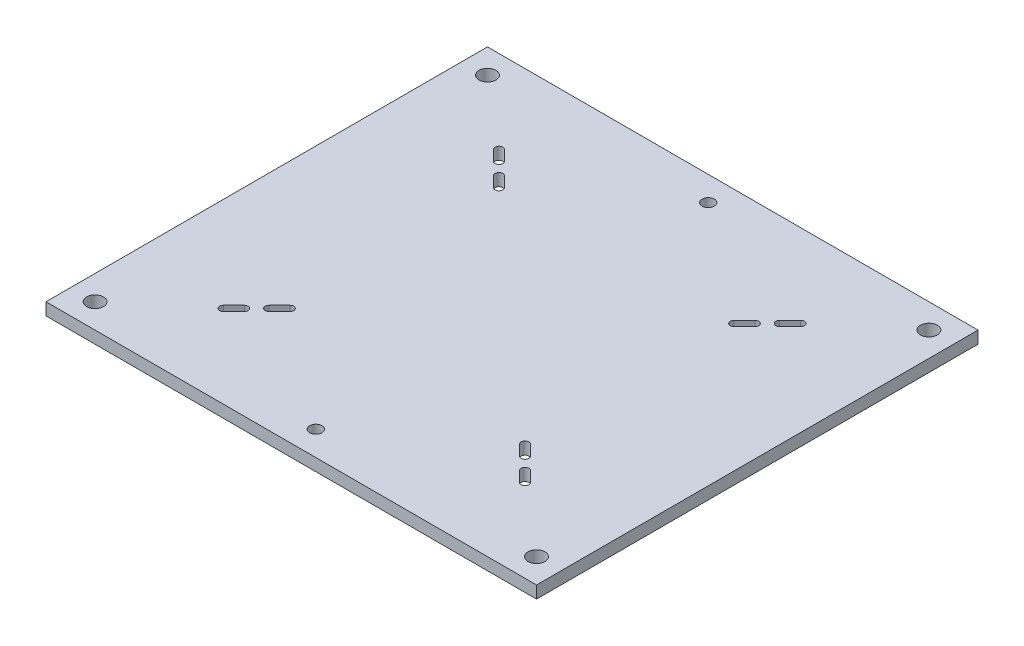
SolidWorks part; units mm, degrees
material "6061-T6 (SS)"
ref_plane "Front Plane" through (0, 0, 0) normal (0, 0, 1) x (1, 0, 0)
ref_plane "Top Plane" through (0, 0, 0) normal (0, 1, 0) x (1, 0, 0)
ref_plane "Right Plane" through (0, 0, 0) normal (1, 0, 0) x (0, 0, -1)
sketch "Sketch1" plane through (0, 0, 0) normal (0, 1, 0) x (1, 0, 0)
  line L1 (0, 0) -> (254, 0)
  line L2 (0, 0) -> (0, -228.6)
  line L3 (0, -228.6) -> (254, -228.6)
  line L4 (254, 0) -> (254, -228.6)
  dimension "D1" = 254
  dimension "D2" = 228.6
extrude "base plate" add sketch "Sketch1" against normal blind 6.35
sketch "center lines" plane through (0, 0, 0) normal (0, 1, 0) x (1, 0, 0)
  line L0 (127, 0) -> (127, -228.6) construction
  line L1 (254, 0) -> (0, 0) construction
  line L2 (0, -228.6) -> (254, -228.6) construction
  line L3 (0, -114.3) -> (254, -114.3) construction
  line L4 (0, 0) -> (0, -228.6) construction
  line L5 (254, -228.6) -> (254, 0) construction
sketch "Sketch3" plane through (0, 0, 0) normal (0, 1, 0) x (1, 0, 0)
  line L0 (36.125, -187.6487) -> (46.9013, -198.425)
  line L1 (46.9013, -198.425) -> (81.0263, -164.3)
  line L2 (81.0263, -164.3) -> (70.25, -153.5237)
  line L3 (70.25, -153.5237) -> (36.125, -187.6487)
  line L4 (48.9222, -185.6278) -> (54.3104, -180.2396) construction
  line L5 (47.508, -184.2135) -> (52.8962, -178.8254)
  line L6 (50.3365, -187.042) -> (55.7246, -181.6538)
  line L7 (0, -228.6) -> (254, -228.6) construction
  line L8 (66.1191, -168.4309) -> (60.7309, -173.8191) construction
  line L9 (67.5333, -169.8451) -> (62.1451, -175.2333)
  line L10 (127, 0) -> (127, -228.6) construction
  line L11 (0, -114.3) -> (254, -114.3) construction
  line L12 (81.0263, -64.3) -> (70.25, -75.0763)
  line L13 (46.9013, -30.175) -> (81.0263, -64.3)
  line L14 (36.125, -40.9513) -> (46.9013, -30.175)
  line L15 (70.25, -75.0763) -> (36.125, -40.9513)
  line L16 (207.0987, -30.175) -> (172.9737, -64.3)
  line L17 (217.875, -40.9513) -> (207.0987, -30.175)
  line L18 (183.75, -75.0763) -> (217.875, -40.9513)
  line L19 (172.9737, -64.3) -> (183.75, -75.0763)
  line L20 (172.9737, -164.3) -> (183.75, -153.5237)
  line L21 (207.0987, -198.425) -> (172.9737, -164.3)
  line L22 (217.875, -187.6487) -> (207.0987, -198.425)
  line L23 (183.75, -153.5237) -> (217.875, -187.6487)
  line L24 (64.7049, -167.0167) -> (59.3167, -172.4049)
  line L25 (48.9222, -42.9722) -> (54.3104, -48.3604) construction
  line L26 (47.508, -44.3865) -> (52.8962, -49.7746)
  line L27 (50.3365, -41.558) -> (55.7246, -46.9462)
  line L28 (66.1191, -60.1691) -> (60.7309, -54.7809) construction
  line L29 (67.5333, -58.7549) -> (62.1451, -53.3667)
  line L30 (64.7049, -61.5833) -> (59.3167, -56.1951)
  line L31 (205.0778, -42.9722) -> (199.6896, -48.3604) construction
  line L32 (206.492, -44.3865) -> (201.1038, -49.7746)
  line L33 (203.6635, -41.558) -> (198.2754, -46.9462)
  line L34 (187.8809, -60.1691) -> (193.2691, -54.7809) construction
  line L35 (186.4667, -58.7549) -> (191.8549, -53.3667)
  line L36 (189.2951, -61.5833) -> (194.6833, -56.1951)
  line L37 (187.8809, -168.4309) -> (193.2691, -173.8191) construction
  line L38 (186.4667, -169.8451) -> (191.8549, -175.2333)
  line L39 (189.2951, -167.0167) -> (194.6833, -172.4049)
  line L40 (205.0778, -185.6278) -> (199.6896, -180.2396) construction
  line L41 (206.492, -184.2135) -> (201.1038, -178.8254)
  line L42 (203.6635, -187.042) -> (198.2754, -181.6538)
  line L43 (70.25, -164.3) -> (70.25, -153.5237)
  line L44 (81.0263, -164.3) -> (70.25, -164.3)
  line L45 (70.25, -64.3) -> (70.25, -75.0763)
  line L46 (81.0263, -64.3) -> (70.25, -64.3)
  line L47 (183.75, -64.3) -> (183.75, -75.0763)
  line L48 (172.9737, -64.3) -> (183.75, -64.3)
  line L49 (183.75, -164.3) -> (183.75, -153.5237)
  line L50 (172.9737, -164.3) -> (183.75, -164.3)
  arc A0 (47.508, -184.2135) -> (50.3365, -187.042) centre (48.9222, -185.6278) ccw
  arc A1 (55.7246, -181.6538) -> (52.8962, -178.8254) centre (54.3104, -180.2396) ccw
  arc A2 (67.5333, -169.8451) -> (64.7049, -167.0167) centre (66.1191, -168.4309) ccw
  arc A3 (59.3167, -172.4049) -> (62.1451, -175.2333) centre (60.7309, -173.8191) ccw
  arc A4 (47.508, -44.3865) -> (50.3365, -41.558) centre (48.9222, -42.9722) cw
  arc A5 (55.7246, -46.9462) -> (52.8962, -49.7746) centre (54.3104, -48.3604) cw
  arc A6 (67.5333, -58.7549) -> (64.7049, -61.5833) centre (66.1191, -60.1691) cw
  arc A7 (59.3167, -56.1951) -> (62.1451, -53.3667) centre (60.7309, -54.7809) cw
  arc A8 (206.492, -44.3865) -> (203.6635, -41.558) centre (205.0778, -42.9722) ccw
  arc A9 (198.2754, -46.9462) -> (201.1038, -49.7746) centre (199.6896, -48.3604) ccw
  arc A10 (186.4667, -58.7549) -> (189.2951, -61.5833) centre (187.8809, -60.1691) ccw
  arc A11 (194.6833, -56.1951) -> (191.8549, -53.3667) centre (193.2691, -54.7809) ccw
  arc A12 (186.4667, -169.8451) -> (189.2951, -167.0167) centre (187.8809, -168.4309) cw
  arc A13 (194.6833, -172.4049) -> (191.8549, -175.2333) centre (193.2691, -173.8191) cw
  arc A14 (206.492, -184.2135) -> (203.6635, -187.042) centre (205.0778, -185.6278) cw
  arc A15 (198.2754, -181.6538) -> (201.1038, -178.8254) centre (199.6896, -180.2396) cw
  point P29 (51.6163, -182.9337)
  point P36 (63.425, -171.125)
  point P44 (51.6163, -45.6663)
  point P51 (63.425, -57.475)
  point P58 (202.3837, -45.6663)
  point P65 (190.575, -57.475)
  point P72 (190.575, -171.125)
  point P79 (202.3837, -182.9337)
  point P84 (55.7246, -178.8254)
  point P85 (59.3167, -175.2333)
  dimension "D6" = 2
  dimension "D10" = 5.08
  dimension "D9" = 5.842
  dimension "D1" = 48.26
  dimension "D2" = 15.24
  dimension "D3" = 45
  dimension "D4" = 100
  dimension "D5" = 113.5
  dimension "D7" = 7.62
  dimension "D8" = 7.62
extrude "slots" cut sketch "Sketch3" against normal through all contours A5 L27 A4 L26 | L33 A9 L32 A8 | L36 A11 L35 A10 | A13 L39 A12 L38 | A15 L42 A14 L41 | L6 A1 L5 A0 | L24 A3 L9 A2 | L30 A7 L29 A6 region at (51.6163, 0, 45.6663) region at (202.3837, 0, 45.6663) region at (190.575, 0, 57.475) region at (190.575, 0, 171.125) region at (202.3837, 0, 182.9337)
hole_wizard "Feet connection hole" positions "Sketch6" profile "Sketch7" hole size "1/4-20" standard "PEM® Inch" end condition through all
sketch "Sketch6" plane through (0, 0, 0) normal (0, 1, 0) x (1, 0, 0)
  line L0 (0, -228.6) -> (254, -228.6) construction
  line L1 (0, 0) -> (0, -228.6) construction
  line L2 (254, -228.6) -> (254, 0) construction
  line L3 (254, 0) -> (0, 0) construction
  point P3 (12.7, -215.9)
  point P19 (241.3, -12.7)
  point P33 (12.7, -12.7)
  point P37 (241.3, -215.9)
  dimension "D1" = 12.7
  dimension "D2" = 12.7
  dimension "D3" = 12.7
  dimension "D4" = 12.7
sketch "Sketch7" plane through (12.7, 0, 215.9) normal (1, 0, 0) x (0, 0, 1)
  line L0 (0, 0) -> (0, 6.35)
  line L1 (0, 6.35) -> (4.3688, 6.35)
  line L2 (4.3688, 6.35) -> (4.3688, 0)
  line L5 (4.3688, 0) -> (0, 0)
  line L11 (0, -6.35) -> (0, 107.95) construction
  dimension "Thru Hole Dia." = 8.7376
  dimension "Thru Hole Depth" = 6.35
hole_wizard "Hole for #10 Blind Fasteners (B,BS)1" positions "Sketch17" profile "Sketch18" hole size "#10-32" standard "PEM® Inch" end condition through all
sketch "Sketch17" plane through (0, 0, 0) normal (0, 1, 0) x (1, 0, 0)
  line L0 (0, -228.6) -> (254, -228.6) construction
  line L1 (254, 0) -> (0, 0) construction
  line L2 (254, -228.6) -> (254, 0) construction
  line L3 (0, 0) -> (0, -228.6) construction
  point P0 (127, -215.9)
  point P2 (127, -12.7)
  dimension "D1" = 12.7
  dimension "D2" = 12.7
  dimension "D3" = 127
  dimension "D4" = 127
sketch "Sketch18" plane through (127, 0, 215.9) normal (1, 0, 0) x (0, 0, 1)
  line L0 (0, 0) -> (0, 6.35)
  line L1 (0, 6.35) -> (3.175, 6.35)
  line L2 (3.175, 6.35) -> (3.175, 0)
  line L5 (3.175, 0) -> (0, 0)
  line L11 (0, -6.35) -> (0, 107.95) construction
  dimension "Thru Hole Dia." = 6.35
  dimension "Thru Hole Depth" = 6.35
